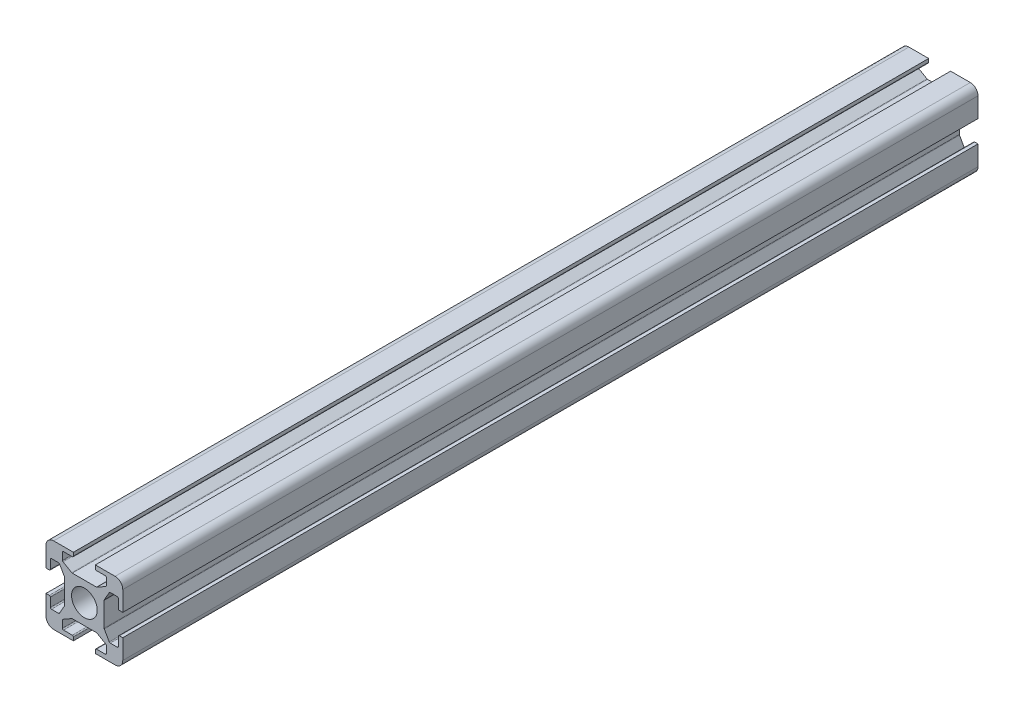
SolidWorks part; units mm, degrees
ref_plane "Alzado" through (0, 0, 0) normal (0, 0, 1) x (1, 0, 0)
ref_plane "Planta" through (0, 0, 0) normal (0, 1, 0) x (1, 0, 0)
ref_plane "Vista lateral" through (0, 0, 0) normal (1, 0, 0) x (0, 0, -1)
sketch "Croquis1" plane through (0, 0, 0) normal (0, 0, 1) x (1, 0, 0)
  line L0 (-10, 0) -> (10, 0) construction
  line L1 (0, 32.431) -> (0, -32.431) construction
  line L2 (-17.5, -5) -> (-16, -5)
  line L3 (-15.5, -15.5) -> (15.5, -15.5) construction
  line L4 (-15.5, -15.5) -> (-15.5, 15.5) construction
  line L5 (17.5, -17.5) -> (17.5, 17.5) construction
  line L6 (-17.5, -17.5) -> (17.5, 17.5) construction
  line L7 (-17.5, 17.5) -> (17.5, -17.5) construction
  line L8 (9, -9) -> (-9, -9) construction
  line L9 (9, -9) -> (9, 9) construction
  line L10 (9, 9) -> (-9, 9) construction
  line L11 (-9, -9) -> (-9, 9) construction
  line L12 (9, -9) -> (-9, 9) construction
  line L13 (9, 9) -> (-9, -9) construction
  line L14 (-15.5, 15.5) -> (15.5, 15.5) construction
  line L15 (15.5, -15.5) -> (15.5, 15.5) construction
  line L16 (-15.5, -15.5) -> (15.5, 15.5) construction
  line L17 (-15.5, 15.5) -> (15.5, -15.5) construction
  line L18 (-14.0807, -14.0828) -> (13.915, 13.9172) construction
  line L19 (-9, 15.5) -> (9, 15.5)
  line L20 (-15.5, -5.5) -> (-15.5, -9.5)
  line L21 (-15, -10) -> (-11.7901, -10)
  line L22 (-11.356, -9.7481) -> (-9.0659, -5.7407)
  line L23 (-9, -5.4926) -> (-9, 5.4926)
  line L24 (-11.356, 9.7481) -> (-9.0659, 5.7407)
  line L25 (-15, 10) -> (-11.7901, 10)
  line L26 (-15.5, 5.5) -> (-15.5, 9.5)
  line L27 (-17.5, 5) -> (-16, 5)
  line L28 (-17.5, 14) -> (-17.5, 5)
  line L29 (-17.5, -5) -> (-17.5, -14)
  line L30 (5, 17.5) -> (5, 16)
  line L31 (-17.5, 17.5) -> (17.5, 17.5) construction
  line L32 (5.5, 15.5) -> (9.5, 15.5)
  line L33 (10, 15) -> (10, 11.7901)
  line L34 (-17.5, -17.5) -> (17.5, -17.5) construction
  line L35 (9.7481, 11.356) -> (5.7407, 9.0659)
  line L36 (-17.5, -17.5) -> (-17.5, 17.5) construction
  line L37 (-17.5, 17.5) -> (17.5, 17.5) construction
  line L38 (17.5, -17.5) -> (17.5, 17.5) construction
  line L39 (-17.5, -17.5) -> (17.5, 17.5) construction
  line L40 (-17.5, 17.5) -> (17.5, -17.5) construction
  line L41 (-5.4926, 9) -> (5.4926, 9)
  line L42 (-9.7481, 11.356) -> (-5.7407, 9.0659)
  line L43 (-10, 15) -> (-10, 11.7901)
  line L44 (-10, -10) -> (10, 10) construction
  line L45 (-10, 10) -> (10, -10) construction
  line L46 (-5.5, 15.5) -> (-9.5, 15.5)
  line L47 (-5, 17.5) -> (-5, 16)
  line L48 (-14, -14) -> (14, 14) construction
  line L49 (-14, 14) -> (14, -14) construction
  line L50 (17.5, -5) -> (16, -5)
  line L51 (15.5, -5.5) -> (15.5, -9.5)
  line L52 (15, -10) -> (11.7901, -10)
  line L53 (11.356, -9.7481) -> (9.0659, -5.7407)
  line L54 (9, 5.4926) -> (9, -5.4926)
  line L55 (11.356, 9.7481) -> (9.0659, 5.7407)
  line L56 (15, 10) -> (11.7901, 10)
  line L57 (15.5, 5.5) -> (15.5, 9.5)
  line L58 (17.5, 5) -> (16, 5)
  line L59 (-5, -17.5) -> (-5, -16)
  line L60 (-5.5, -15.5) -> (-9.5, -15.5)
  line L61 (-10, -15) -> (-10, -11.7901)
  line L62 (-9.7481, -11.356) -> (-5.7407, -9.0659)
  line L63 (5.4926, -9) -> (-5.4926, -9)
  line L64 (9.7481, -11.356) -> (5.7407, -9.0659)
  line L65 (10, -15) -> (10, -11.7901)
  line L66 (5.5, -15.5) -> (9.5, -15.5)
  line L67 (5, -17.5) -> (5, -16)
  line L68 (-5, 17.5) -> (-14, 17.5)
  line L69 (5, 17.5) -> (14, 17.5)
  line L70 (17.5, 14) -> (17.5, 5)
  line L71 (17.5, -5) -> (17.5, -14)
  line L72 (14, -17.5) -> (5, -17.5)
  line L73 (-14, -17.5) -> (-5, -17.5)
  circle A0 centre (0, 0) radius 5.85
  arc A1 (-9.0659, -5.7407) -> (-9, -5.4926) centre (-9.5, -5.4926) ccw
  arc A2 (-11.7901, -10) -> (-11.356, -9.7481) centre (-11.7901, -9.5) ccw
  arc A3 (-15.5, -9.5) -> (-15, -10) centre (-15, -9.5) ccw
  arc A4 (-16, -5) -> (-15.5, -5.5) centre (-16, -5.5) cw
  arc A5 (-11.7901, 10) -> (-11.356, 9.7481) centre (-11.7901, 9.5) cw
  arc A6 (-15.5, 9.5) -> (-15, 10) centre (-15, 9.5) cw
  arc A7 (-16, 5) -> (-15.5, 5.5) centre (-16, 5.5) ccw
  arc A8 (-9.0659, 5.7407) -> (-9, 5.4926) centre (-9.5, 5.4926) cw
  arc A9 (5, 16) -> (5.5, 15.5) centre (5.5, 16) ccw
  arc A10 (9.5, 15.5) -> (10, 15) centre (9.5, 15) cw
  arc A11 (10, 11.7901) -> (9.7481, 11.356) centre (9.5, 11.7901) cw
  arc A12 (5.7407, 9.0659) -> (5.4926, 9) centre (5.4926, 9.5) cw
  arc A13 (-5.7407, 9.0659) -> (-5.4926, 9) centre (-5.4926, 9.5) ccw
  arc A14 (-10, 11.7901) -> (-9.7481, 11.356) centre (-9.5, 11.7901) ccw
  arc A15 (-9.5, 15.5) -> (-10, 15) centre (-9.5, 15) ccw
  arc A16 (-5, 16) -> (-5.5, 15.5) centre (-5.5, 16) cw
  arc A17 (16, -5) -> (15.5, -5.5) centre (16, -5.5) ccw
  arc A18 (15.5, -9.5) -> (15, -10) centre (15, -9.5) cw
  arc A19 (11.7901, -10) -> (11.356, -9.7481) centre (11.7901, -9.5) cw
  arc A20 (9.0659, -5.7407) -> (9, -5.4926) centre (9.5, -5.4926) cw
  arc A21 (9.0659, 5.7407) -> (9, 5.4926) centre (9.5, 5.4926) ccw
  arc A22 (11.7901, 10) -> (11.356, 9.7481) centre (11.7901, 9.5) ccw
  arc A23 (15.5, 9.5) -> (15, 10) centre (15, 9.5) ccw
  arc A24 (16, 5) -> (15.5, 5.5) centre (16, 5.5) cw
  arc A25 (-5, -16) -> (-5.5, -15.5) centre (-5.5, -16) ccw
  arc A26 (-9.5, -15.5) -> (-10, -15) centre (-9.5, -15) cw
  arc A27 (-10, -11.7901) -> (-9.7481, -11.356) centre (-9.5, -11.7901) cw
  arc A28 (-5.7407, -9.0659) -> (-5.4926, -9) centre (-5.4926, -9.5) cw
  arc A29 (5.7407, -9.0659) -> (5.4926, -9) centre (5.4926, -9.5) ccw
  arc A30 (10, -11.7901) -> (9.7481, -11.356) centre (9.5, -11.7901) ccw
  arc A31 (9.5, -15.5) -> (10, -15) centre (9.5, -15) ccw
  arc A32 (5, -16) -> (5.5, -15.5) centre (5.5, -16) cw
  arc A33 (17.5, -14) -> (14, -17.5) centre (14, -14) cw
  arc A34 (14, 17.5) -> (17.5, 14) centre (14, 14) cw
  arc A35 (-14, 17.5) -> (-17.5, 14) centre (-14, 14) ccw
  arc A36 (-17.5, -14) -> (-14, -17.5) centre (-14, -14) ccw
  point P0 (0, 0)
  point P4 (0, 0)
  point P31 (0, 0)
  point P37 (-11.5, -10)
  point P48 (-15.5, -10)
  point P50 (0, -15.5)
  point P53 (-9, 0)
  point P56 (0, 15.5172)
  point P149 (0, 0)
  dimension "D3" = 11.7
  dimension "D11" = 0.5
  dimension "D12" = 4
  dimension "D13" = 3.5
  dimension "D14" = 3.5
  dimension "D1" = 35
  dimension "D2" = 35
  dimension "D4" = 18
  dimension "D5" = 18
  dimension "D6" = 31
  dimension "D7" = 10
  dimension "D8" = 20
  dimension "D9" = 4
  dimension "D10" = 35
extrude "Saliente-Extruir1" add sketch "Croquis1" along normal blind 390 contours L29 A36 L73 L59 A25 L60 A26 L61 A27 L62 A28 L63 A29 L64 A30 L65 A31 L66 A32 L67 L72 A33 L71 L50 A17 L51 A18 L52 A19 L53 A20 L54 A21 L55 A22 L56 A23 L57 A24 L58 L70 A34 L69 L30 A9 L19 L32 A10 L33 A11 L35 region at (-16.75, -5.495, 0)
